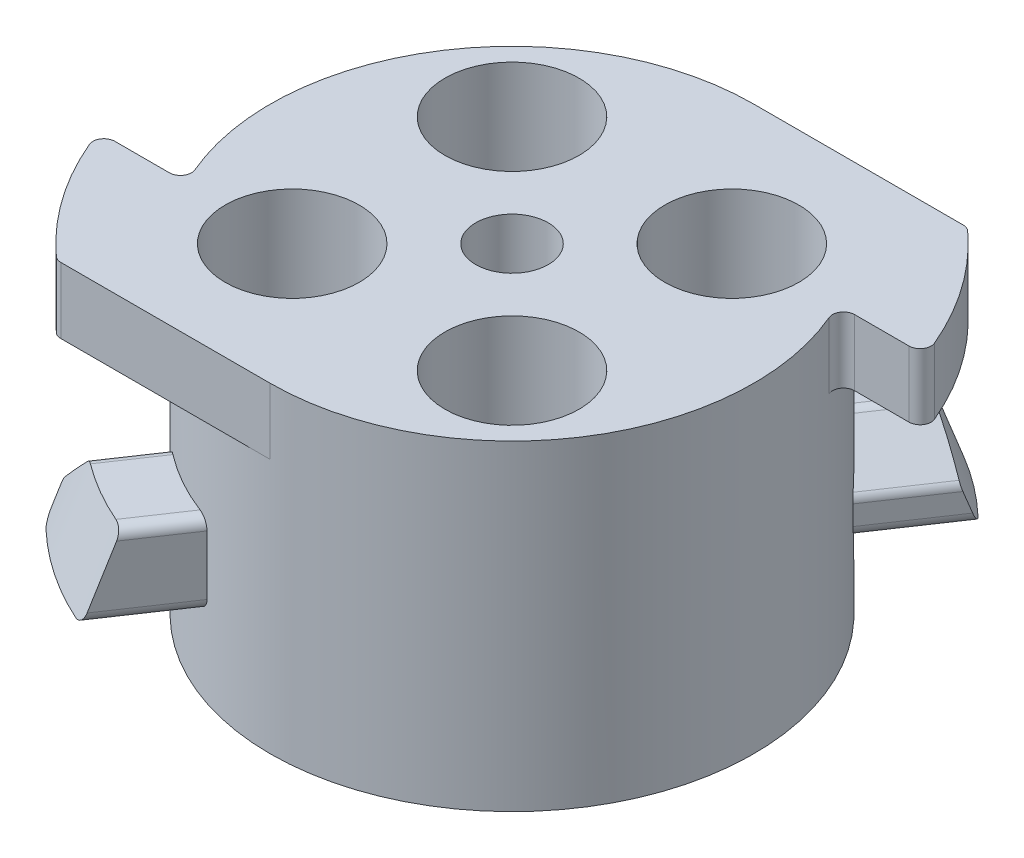
SolidWorks part; units mm, degrees
ref_plane "Front Plane" through (0, 0, 0) normal (0, 0, 1) x (1, 0, 0)
ref_plane "Top Plane" through (0, 0, 0) normal (0, 1, 0) x (1, 0, 0)
ref_plane "Right Plane" through (0, 0, 0) normal (1, 0, 0) x (0, 0, -1)
sketch "Sketch2" plane through (0, 0, 0) normal (0, 1, 0) x (1, 0, 0)
  line L0 (5, 5) -> (-5, -5) construction
  line L1 (-5, 5) -> (5, -5) construction
  line L2 (3.4202, 10.4548) -> (8.5413, 18.0637)
  line L3 (13.5189, 14.7136) -> (8.3978, 7.1047)
  line L4 (-3.4202, -10.4548) -> (-8.5413, -18.0637)
  line L5 (-8.3978, -7.1047) -> (-13.5189, -14.7136)
  line L6 (3.4202, 10.4548) -> (3.4202, 19.6863)
  line L7 (-3.4202, -10.4548) -> (-3.4202, -19.6863)
  line L8 (3.4202, 10.4548) -> (8.3978, 7.1047)
  line L9 (-8.3978, -7.1047) -> (-3.4202, -10.4548)
  line L10 (5.909, 8.7797) -> (0, 0) construction
  circle A0 centre (0, 0) radius 11
  circle A10 centre (-5, 5) radius 3.05
  circle A11 centre (5, 5) radius 3.05
  circle A12 centre (5, -5) radius 3.05
  circle A13 centre (-5, -5) radius 3.05
  circle A15 centre (0, 0) radius 1.65
  circle A16 centre (0, 0) radius 13
  circle A17 centre (0, 0) radius 19.9812
  circle A18 centre (0, 0) radius 2.94
  circle A19 centre (0, 0) radius 15.1
  dimension "D1" = 22
  dimension "D2" = 6.1
  dimension "D3" = 26
  dimension "D7" = 3.3
  dimension "D8" = 39.9625
  dimension "D6" = 5.88
  dimension "D11" = 30.2
  dimension "D4" = 10
  dimension "D5" = 6
  dimension "D9" = 33.942
extrude "Boss-Extrude2" add sketch "Sketch2" along normal blind 11.6 contours A0 A18 A13 A12 A11 A10 | A18 A15 | L9 A0 | L8 A0 region at (6.0023, 0, -8.9183) region at (5.7353, 0, -8.5216) region at (-6.0023, 0, 8.9183) region at (-2.8568, 0, 0)
extrude "Boss-Extrude3" add sketch "Sketch2<10>" along normal blind 0.4 contours A11 | A10 | A12 | A13 region at (-5, 0, -5) region at (5, 0, -5) region at (5, 0, 5) region at (-5, 0, 5)
sketch "Sketch2<10>" plane through (0, 0, 0) normal (0, 1, 0) x (1, 0, 0) same geometry as "Sketch2"
extrude "Cut-Extrude1" cut sketch "Sketch2<13>" along normal blind 6 contours A18 A15 region at (-2.8568, 0, 0)
sketch "Sketch2<13>" plane through (0, 0, 0) normal (0, 1, 0) x (1, 0, 0) same geometry as "Sketch2"
extrude "Boss-Extrude4" add sketch "Sketch2<15>" along normal blind 7.3 contours L3 A16 L2 A0 | L3 A19 L2 A16 | L5 A16 L4 A0 | L5 A19 L4 A16 region at (6.6286, 0, -9.8489) region at (7.7841, 0, -11.5657) region at (-6.6286, 0, 9.8489) region at (-7.7841, 0, 11.5657)
sketch "Sketch2<15>" plane through (0, 0, 0) normal (0, 1, 0) x (1, 0, 0) same geometry as "Sketch2"
extrude "Cut-Extrude2" cut sketch "Sketch2<16>" along normal blind 3.6 contours L3 A19 L2 A16 | L3 A16 L2 A0 | L5 A16 L4 A0 | L5 A19 L4 A16 region at (6.6286, 0, -9.8489) region at (7.7841, 0, -11.5657) region at (-6.6286, 0, 9.8489) region at (-7.7841, 0, 11.5657)
sketch "Sketch2<16>" plane through (0, 0, 0) normal (0, 1, 0) x (1, 0, 0) same geometry as "Sketch2"
chamfer "Chamfer1" distance 2.1 angle 45 2 edges at (9.5748, 7.3, -8.8535) (-9.5748, 7.3, 8.8535)
chamfer "Chamfer2" distance 4 distance2 1.4 2 edges at (7.5319, 7.3, -13.0874) (-7.5319, 7.3, 13.0874) first distance on face at (8.4942, 5.399, -12.2999) first distance on face at (-8.4942, 5.399, 12.2999)
sketch "Sketch3" plane through (0, 11.6, 0) normal (0, 1, 0) x (1, 0, 0)
  line L0 (9.798, 5) -> (13.798, 5)
  line L1 (0, 11) -> (9.7151, 11)
  line L2 (-9.798, -5) -> (-13.798, -5)
  line L3 (0, -11) -> (-9.7151, -11)
  circle A0 centre (0, 0) radius 11
  circle A1 centre (5, 5) radius 3.05
  circle A2 centre (-5, 5) radius 3.05
  circle A3 centre (0, 0) radius 1.45
  circle A4 centre (5, -5) radius 3.05
  circle A5 centre (-5, -5) radius 3.05
  arc A6 (13.798, 5) -> (9.7151, 11) centre (0, 0) ccw
  arc A8 (-13.798, -5) -> (-9.7151, -11) centre (0, 0) ccw
  circle M6 centre (-5, -5) radius 3.05
  circle M7 centre (5, -5) radius 3.05
  circle M8 centre (5, 5) radius 3.05
  circle M9 centre (-5, 5) radius 3.05
  circle M10 centre (0, 0) radius 11
  circle M11 centre (0, 0) radius 1.65
  dimension "D1" = 6.1
  dimension "D2" = 2.9
  dimension "D3" = 22
  dimension "D4" = 5
  dimension "D6" = 4
extrude "Boss-Extrude5" add sketch "Sketch3" along normal blind 3 contours M10 M7 M9 M11 M8 M6 | L0 A6 L1 M10 | L2 A8 L3 M10 region at (9.2051, 11.6, -8.3371) region at (10.3928, 11.6, -2.4985) region at (-9.2051, 11.6, 8.3371)
fillet "Fillet1" radius 0.5 16 edges at (-9.5449, 3.6, 8.809) (-4.5673, 3.6, 12.1591) (-4.1976, 7.3, 11.6098) (-7.6237, 7.3, 9.7155) (-9.3852, 5.2, 8.5717) (4.5673, 3.6, -12.1591) (4.1976, 7.3, -11.6098) (9.5449, 3.6, -8.809) (7.6237, 7.3, -9.7155) (9.3852, 5.2, -8.5717) (9.798, 13.1, -5) (13.798, 13.1, -5) (9.7151, 13.1, -11) (-9.7151, 13.1, 11) (-13.798, 13.1, 5) (-9.798, 13.1, 5)
